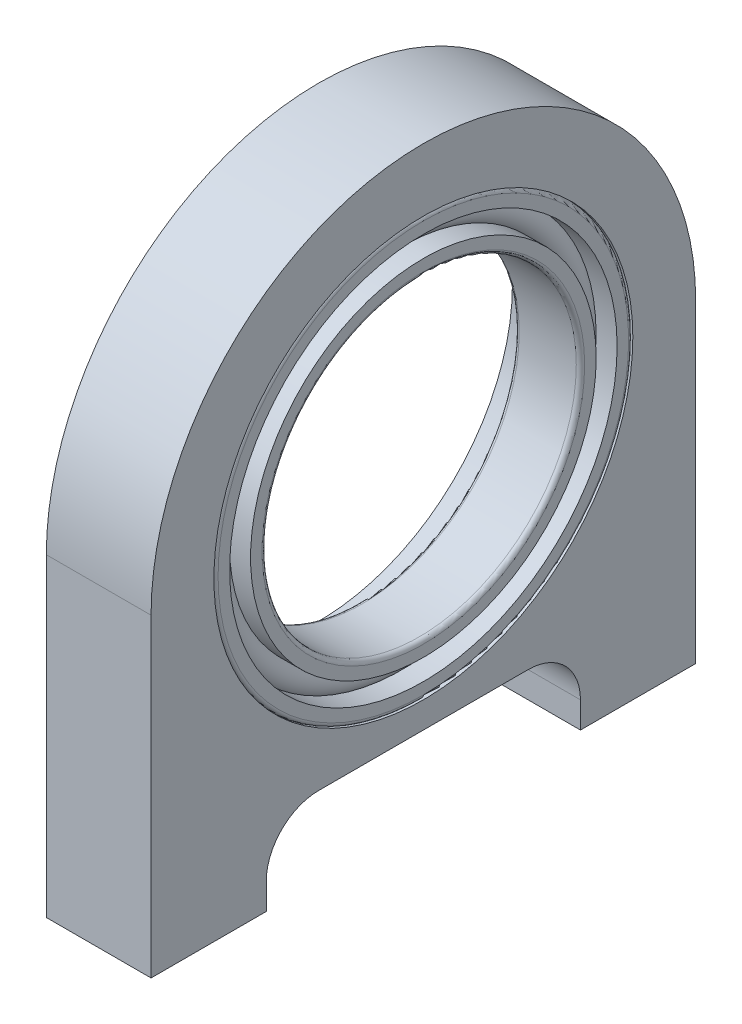
SolidWorks part; units mm, degrees
material "6061 Alloy"
ref_plane "Plane1" through (0, 0, 0) normal (0, 0, 1) x (1, 0, 0)
ref_plane "Plane2" through (0, 0, 0) normal (0, 1, 0) x (1, 0, 0)
ref_plane "Plane3" through (0, 0, 0) normal (1, 0, 0) x (0, 0, -1)
sketch "Clipboard" plane through (0, 0, 0) normal (0, 0, 1) x (1, 0, 0)
  line L0 (-10, 0) -> (10, 0) construction
  line L1 (0, 0) -> (22.3471, -0.7804)
  line L2 (0, 0) -> (11.1057, 0.3878)
  line L3 (0, 0) -> (22.3471, -0.7804)
  line L4 (0, 0) -> (-22.3573, -0.3902)
  dimension "BallCLRad" = 11.1125
  dimension "Count" = 2
  dimension "Show_count" = 2
  dimension "Max_count" = 2
  dimension "Min_count" = 1
sketch "CagSpiSke" plane through (0, 0, 0) normal (0, 0, 1) x (1, 0, 0)
  line L0 (0.0952, 10.9537) -> (0.0953, 11.2712)
  line L1 (0.0953, 11.2712) -> (-0.0953, 11.2712)
  line L2 (-0.0953, 11.2712) -> (-0.0952, 10.9537)
  line L3 (-0.0952, 10.9537) -> (0.0952, 10.9537)
  line L4 (-20.6375, 0) -> (20.6375, 0) construction
  line L5 (0, 0) -> (0, 23.7692) construction
  dimension "Thickness" = 0.1905
  dimension "OD" = 22.5425
  dimension "ID" = 21.9075
revolve "CageSpine" add sketch "CagSpiSke" angle 0.001 about L4 reverse direction yes
ref_axis "Axis1" through (-50, 0, 0) along (1, 0, 0)
sketch "CagBalSke" plane through (0, 0, 0) normal (0, 0, 1) x (1, 0, 0)
  line L0 (-1.0478, 11.1125) -> (1.0478, 11.1125)
  line L1 (-1.905, 11.1125) -> (1.905, 11.1125) construction
  line L2 (-10, 0) -> (10, 0) construction
  line L3 (0, 0) -> (0, 24) construction
  arc A0 (1.0478, 11.1125) -> (-1.0478, 11.1125) centre (0, 11.1125) cw
  dimension "CageWallOD" = 2.0955
  dimension "BallCLRad" = 11.1125
sketch "CagTrmODSke" plane through (0, 0, 0) normal (0, 0, 1) x (1, 0, 0)
  line L0 (1.0732, 11.2712) -> (1.0732, 12.1856)
  line L1 (1.0732, 12.1856) -> (-1.0732, 12.1856)
  line L2 (-1.0732, 12.1856) -> (-1.0732, 11.2712)
  line L3 (-1.0732, 11.2712) -> (1.0732, 11.2712)
  line L4 (-20.6375, 0) -> (20.6375, 0) construction
  line L5 (0, 0) -> (0, 25) construction
  dimension "Width" = 2.1463
  dimension "ID" = 22.5425
  dimension "OD" = 24.3713
sketch "CagTrmIDSke" plane through (0, 0, 0) normal (0, 0, 1) x (1, 0, 0)
  line L0 (1.0732, 10.0901) -> (1.0732, 10.9538)
  line L1 (1.0732, 10.9538) -> (-1.0732, 10.9538)
  line L2 (-1.0732, 10.9538) -> (-1.0732, 10.0901)
  line L3 (-1.0732, 10.0901) -> (1.0732, 10.0901)
  line L4 (-20.6375, 0) -> (20.6375, 0) construction
  line L5 (0, 0) -> (0, 25) construction
  dimension "ID" = 20.1803
  dimension "OD" = 21.9075
  dimension "Width" = 2.1463
sketch "BalSimSke" plane through (0, 0, 0) normal (0, 0, 1) x (1, 0, 0)
  line L0 (-10, 0) -> (10, 0) construction
  line L1 (-10, 11.1125) -> (10, 11.1125) construction
  line L2 (0, 0) -> (0, 23) construction
  circle A0 centre (0, 11.1125) radius 0.9525
  dimension "Ball_diameter" = 1.905
  dimension "BallCLRad" = 11.1125
revolve "BallsSimplified" add sketch "BalSimSke" angle 360 about L0
sketch "BalDetSke" plane through (0, 0, 0) normal (0, 0, 1) x (1, 0, 0)
  line L0 (-0.9525, 11.1125) -> (0.9525, 11.1125)
  line L1 (-1.905, 11.1125) -> (1.905, 11.1125) construction
  line L2 (0, 0) -> (0, 25) construction
  arc A0 (0.9525, 11.1125) -> (-0.9525, 11.1125) centre (0, 11.1125) cw
  dimension "Ball_diameter" = 1.905
  dimension "BallCLRad" = 11.1125
sketch "InnRacSke" plane through (0, 0, 0) normal (0, 0, 1) x (1, 0, 0)
  line L0 (-0.6501, 10.4775) -> (-1.9837, 10.4775)
  line L1 (-1.9837, 10.4775) -> (-1.9837, 9.779)
  line L2 (-1.7297, 9.525) -> (1.7297, 9.525)
  line L3 (1.9837, 9.779) -> (1.9837, 10.4775)
  line L4 (1.9837, 10.4775) -> (0.7009, 10.4775)
  line L5 (-20.6375, 0) -> (20.6375, 0) construction
  line L6 (0, 0) -> (0, 30) construction
  arc A0 (-1.9837, 9.779) -> (-1.7297, 9.525) centre (-1.7297, 9.779) ccw
  arc A1 (1.7297, 9.525) -> (1.9837, 9.779) centre (1.7297, 9.779) ccw
  arc A2 (0.7009, 10.4775) -> (-0.6501, 10.4775) centre (0.0254, 11.1125) cw
  dimension "Fillet_radius" = 0.254
  dimension "Ball_diameter" = 1.8542
  dimension "ID" = 19.05
  dimension "OD" = 20.955
  dimension "Width" = 3.9675
  dimension "BallCLRad" = 11.1125
  dimension "Skew" = 0.0254
revolve "InnerRace" add sketch "InnRacSke" angle 360 about L5 reverse direction yes
sketch "OutRacSke" plane through (0, 0, 0) normal (0, 0, 1) x (1, 0, 0)
  line L0 (-0.6755, 11.7475) -> (-1.9837, 11.7475)
  line L1 (-1.9837, 11.7475) -> (-1.9837, 12.446)
  line L2 (-1.7297, 12.7) -> (1.7297, 12.7)
  line L3 (1.9837, 12.446) -> (1.9837, 11.7475)
  line L4 (1.9837, 11.7475) -> (0.6755, 11.7475)
  line L5 (-20.6375, 0) -> (20.6375, 0) construction
  line L6 (0, 0) -> (0, 30) construction
  arc A0 (-1.9837, 12.446) -> (-1.7297, 12.7) centre (-1.7297, 12.446) cw
  arc A1 (1.7297, 12.7) -> (1.9837, 12.446) centre (1.7297, 12.446) cw
  arc A2 (0.6755, 11.7475) -> (-0.6755, 11.7475) centre (0, 11.1125) ccw
  dimension "Fillet_radius" = 0.254
  dimension "Ball_diameter" = 1.8542
  dimension "OD" = 25.4
  dimension "ID" = 23.495
  dimension "Width" = 3.9675
  dimension "BallCLRad" = 11.1125
revolve "OuterRace" add sketch "OutRacSke" angle 360 about L5 reverse direction yes
sketch "Sketch1" plane through (1.9837, 0, 0) normal (1, 0, 0) x (0, 0, -1)
  line L0 (0, 16.51) -> (0, -19.05) construction
  line L1 (-16.51, 0) -> (-16.51, -19.05)
  line L2 (16.51, 0) -> (16.51, -19.05)
  line L3 (16.51, -19.05) -> (9.525, -19.05)
  line L4 (6.35, -14.2875) -> (-6.35, -14.2875)
  line L5 (-9.525, -17.4625) -> (-9.525, -19.05)
  line L6 (9.525, -17.4625) -> (9.525, -19.05)
  line L7 (-9.525, -19.05) -> (-16.51, -19.05)
  circle A0 centre (0, 0) radius 12.7
  arc A1 (16.51, 0) -> (-16.51, 0) centre (0, 0) ccw
  arc A2 (9.525, -17.4625) -> (6.35, -14.2875) centre (6.35, -17.4625) ccw
  arc A3 (-6.35, -14.2875) -> (-9.525, -17.4625) centre (-6.35, -17.4625) ccw
  point P13 (0, -14.2875)
  point P17 (9.525, -14.2875)
  point P20 (-9.525, -14.2875)
  dimension "D1" = 33.02
  dimension "D3" = 25.4
  dimension "D6" = 3.175
  dimension "D2" = 19.05
  dimension "D4" = 4.7625
  dimension "D5" = 19.05
extrude "Boss-Extrude1" add sketch "Sketch1" against normal blind 6.35
sketch "Sketch2" plane through (-4.3663, 0, 0) normal (-1, 0, 0) x (0, 0, 1)
  circle A0 centre (0, 0) radius 12.7
  circle A1 centre (0, 0) radius 11.7475
extrude "Boss-Extrude2" add sketch "Sketch2" against normal up to surface (2.3825 mm away) up to face at (-1.9837, 0, -11.7475)
hole_wizard "#6-32 Tapped Hole1" positions "Sketch4" profile "Sketch3" tap size "#6-32" standard "Ansi Inch"
sketch "Sketch4" plane through (0, -19.05, 0) normal (0, -1, 0) x (1, 0, 0)
  line L0 (-1.1913, 13.4704) -> (-1.1913, -13.4704) construction
  line L1 (-1.1913, 13.4704) -> (12.2791, 0) construction
  line L2 (12.2791, 0) -> (-1.1913, -13.4704) construction
  line L3 (-4.3663, 6.35) -> (-4.3663, -6.35) construction
  line L4 (12.2791, 0) -> (-1.1913, 0) construction
  point P0 (-1.1913, 13.4704)
  point P1 (-1.1913, -13.4704)
  point P15 (-1.1913, 0)
  dimension "D1" = 3.175
  dimension "D2" = 19.05
  dimension "D3" = 19.05
sketch "Sketch3" plane through (-1.1913, -19.05, 13.4704) normal (1, 0, 0) x (0, 0, -1)
  line L0 (0, 0) -> (0, 10.2005)
  line L1 (0, 10.2005) -> (1.3525, 9.3878)
  line L2 (1.3525, 9.3878) -> (1.3525, 0)
  line L5 (1.3525, 0) -> (0, 0)
  line L10 (0, 10.2005) -> (-1.3526, 9.3878) construction
  line L11 (0, -6.35) -> (0, 107.95) construction
  dimension "Tap Drill Dia." = 2.7051
  dimension "Tap Drill Depth" = 9.3878
  dimension "Drill Angle" = 118
cosmetic thread "Hole Thread1"
cosmetic thread "Hole Thread2"
equation "\"BallCLRad@Clipboard\" = ( \"OD@OutRacSke\" + \"ID@InnRacSke\" ) / 4"
equation "\"BallCLRad@BalSimSke\" = \"BallCLRad@Clipboard\""
equation "\"BallCLRad@BalDetSke\" = \"BallCLRad@Clipboard\""
equation "\"BallCLRad@InnRacSke\" = \"BallCLRad@Clipboard\""
equation "\"BallCLRad@OutRacSke\" = \"BallCLRad@Clipboard\""
equation "\"Ball_diameter@InnRacSke\" = \"Ball_diameter@BalDetSke\" - 0.002"
equation "\"Ball_diameter@OutRacSke\" = \"Ball_diameter@BalDetSke\" - 0.002"
equation "\"Ball_diameter@BalSimSke\" = \"Ball_diameter@BalDetSke\""
equation "\"Width@OutRacSke\" = \"Width@InnRacSke\""
equation "\"Fillet_radius@OutRacSke\" = \"Fillet_radius@InnRacSke\""
equation "\"Max_count@Clipboard\" = int( 3.14159265 / atn(( \"Ball_diameter@BalDetSke\" / 2) / sqr( \"BallCLRad@Clipboard\"  *  \"BallCLRad@Clipboard\" - ( \"Ball_diameter@BalDetSke\" / 2) *  ( \"Ball_diameter@BalDetSke\" / 2))))"
equation "\"Max_count@Clipboard\" = ((sgn( \"Max_count@Clipboard\" - \"Count@Clipboard\" )-1)*( \"Max_count@Clipboard\" - \"Count@Clipboard\" ))/-2+ \"Count@Clipboard\""
equation "\"Count@BallsDetailed\" = int( \"Show_count@Clipboard\" ) "
equation "\"Count@BallsDetailed\" = ((sgn( \"Count@BallsDetailed\" - \"Max_count@Clipboard\" )-1)*( \"Count@BallsDetailed\" - \"Max_count@Clipboard\" ))/-2+ \"Max_count@Clipboard\""
equation "\"Count@BallsDetailed\" = ((sgn( \"Count@BallsDetailed\" - \"Min_count@Clipboard\" )+1)*( \"Count@BallsDetailed\" - \"Min_count@Clipboard\"))/2 +\"Min_count@Clipboard\""
equation "\"Angle@BallsDetailed\" = 360.0 / \"Max_count@Clipboard\""
equation "\"BallCLRad@CagBalSke\" = \"BallCLRad@Clipboard\""
equation "\"Count@CageBalls\" = \"Count@BallsDetailed\""
equation "\"Angle@CageBalls\" = \"Angle@BallsDetailed\""
equation "\"Angle@CageSpine\" =  \"Angle@CageBalls\" * ( \"Count@CageBalls\" -1 + int( \"Count@CageBalls\" / \"Max_count@Clipboard\" ) )  + 0.001 -  int( \"Count@CageBalls\" / \"Max_count@Clipboard\" ) * 0.001"
equation "\"Angle@CageSpine\" =  \"Angle@CageSpine\" * int( \"Min_count@Clipboard\" / 2) + int(1 / \"Min_count@Clipboard\")  * 0.001"
equation "\"CageWallOD@CagBalSke\" =  \"Ball_diameter@BalDetSke\" * 1.1"
equation "\"Thickness@CagSpiSke\" =  \"Ball_diameter@BalDetSke\" * 0.1"
equation "\"OD@CagTrmODSke\" = \"BallCLRad@Clipboard\" * 2 + \"CageWallOD@CagBalSke\" + 0.002"
equation "\"ID@CagTrmODSke\" = \"BallCLRad@Clipboard\" * 2 + \"Ball_diameter@BalDetSke\" / 6"
equation "\"OD@CagTrmIDSke\" = \"BallCLRad@Clipboard\" * 2 - \"Ball_diameter@BalDetSke\" / 6"
equation "\"ID@CagTrmIDSke\" = \"BallCLRad@Clipboard\" * 2 - \"CageWallOD@CagBalSke\" + 0.002"
equation "\"OD@CagSpiSke\" = \"ID@CagTrmODSke\""
equation "\"ID@CagSpiSke\" = \"OD@CagTrmIDSke\""
equation "\"Width@CagTrmODSke\" = \"CageWallOD@CagBalSke\" + 0.002"
equation "\"Width@CagTrmIDSke\" = \"CageWallOD@CagBalSke\" + 0.002"
